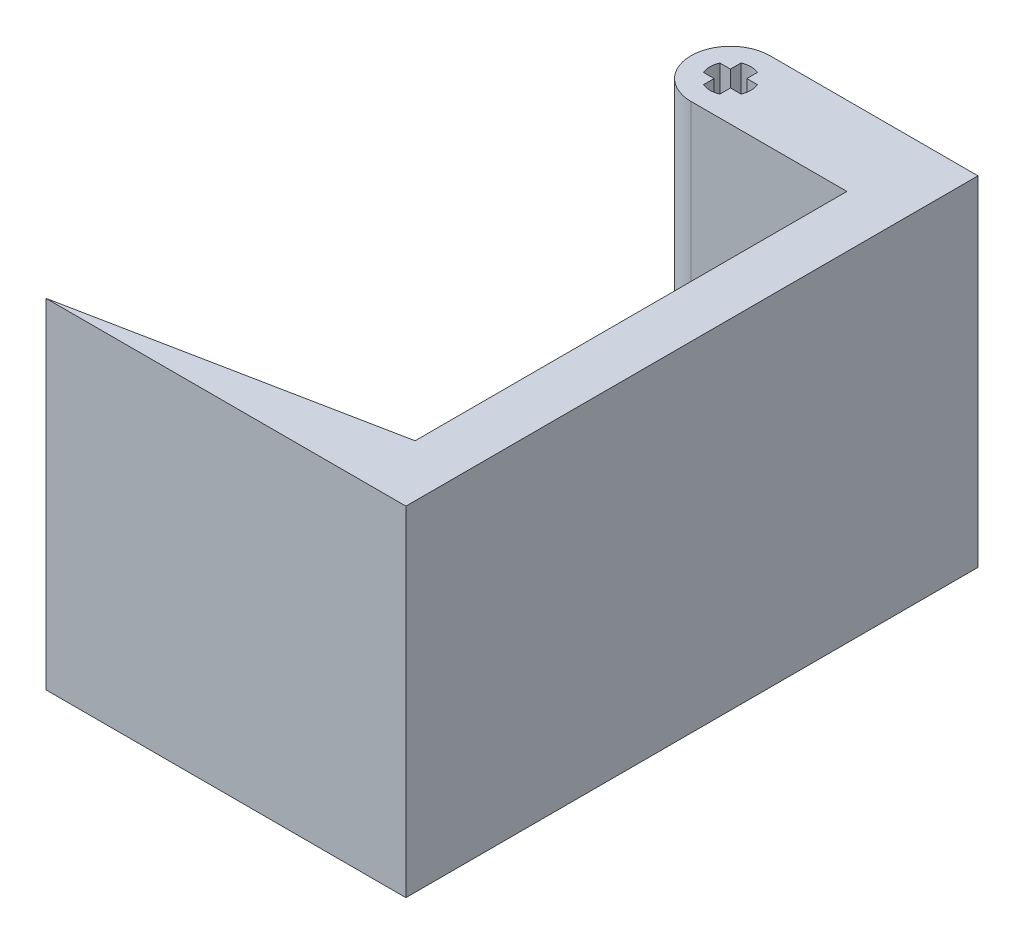
SolidWorks part; units mm, degrees
ref_plane "Front Plane" through (0, 0, 0) normal (0, 0, 1) x (1, 0, 0)
ref_plane "Top Plane" through (0, 0, 0) normal (0, 1, 0) x (1, 0, 0)
ref_plane "Right Plane" through (0, 0, 0) normal (1, 0, 0) x (0, 0, -1)
sketch "Sketch1" plane through (0, 0, 0) normal (0, 1, 0) x (1, 0, 0)
  line L0 (-1, 1) -> (-2.2913, 1)
  line L1 (-1, -1) -> (-2.2913, -1)
  line L2 (1, 1) -> (1, 2.2913)
  line L3 (-1, 1) -> (-1, 2.2913)
  line L4 (1, -1) -> (2.2913, -1)
  line L5 (1, 1) -> (2.2913, 1)
  line L6 (-1, -1) -> (-1, -2.2913)
  line L7 (1, -1) -> (1, -2.2913)
  line L8 (25.4, 4.826) -> (0, 4.826)
  line L9 (19.05, -4.826) -> (0, -4.826)
  line L10 (25.4, 4.826) -> (25.4, -65.024)
  line L11 (25.4, -65.024) -> (-18.542, -65.024)
  line L12 (-18.542, -65.024) -> (19.05, -57.5506)
  line L13 (19.05, -57.5506) -> (19.05, -4.826)
  arc A0 (-2.2913, 1) -> (-2.2913, -1) centre (0, 0) ccw
  arc A1 (1, 2.2913) -> (-1, 2.2913) centre (0, 0) ccw
  arc A2 (2.2913, -1) -> (2.2913, 1) centre (0, 0) ccw
  arc A3 (-1, -2.2913) -> (1, -2.2913) centre (0, 0) ccw
  arc A4 (0, -4.826) -> (0, 4.826) centre (0, 0) cw
  point P13 (0, 0)
  dimension "D1" = 5
  dimension "D7" = 4.826
  dimension "D8" = 57.5506
  dimension "D2" = 1
  dimension "D3" = 6.35
  dimension "D4" = 69.85
  dimension "D5" = 25.4
  dimension "D6" = 43.942
extrude "Boss-Extrude6" add sketch "Sketch1" along normal blind 41.402
